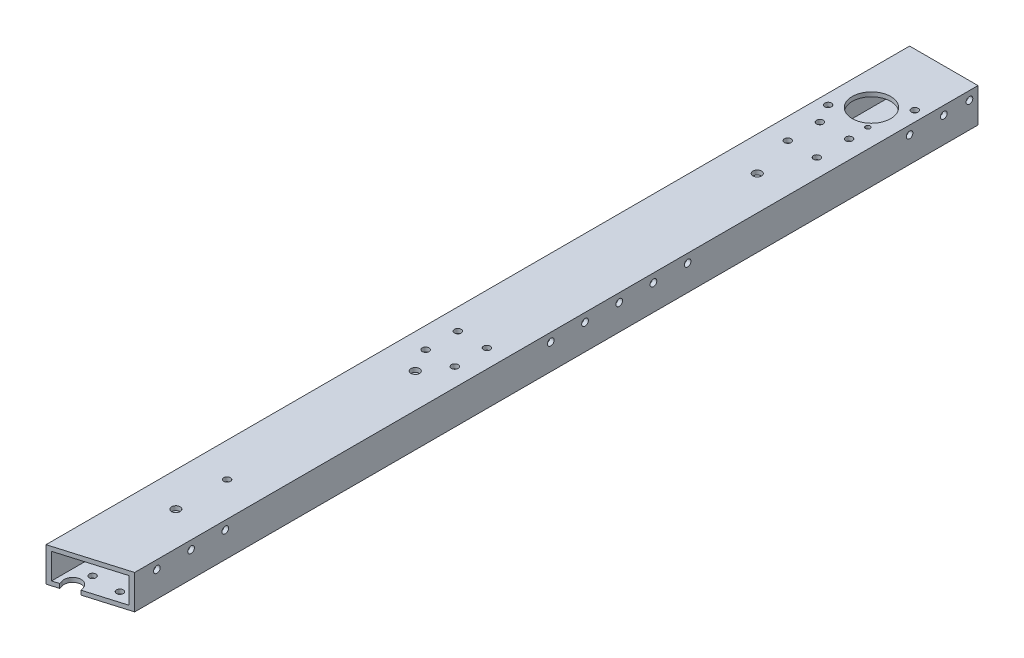
SolidWorks part; units mm, degrees
material "6061 Alloy"
ref_plane "Front Plane" through (0, 0, 0) normal (0, 0, 1) x (1, 0, 0)
ref_plane "Top Plane" through (0, 0, 0) normal (0, 1, 0) x (1, 0, 0)
ref_plane "Right Plane" through (0, 0, 0) normal (1, 0, 0) x (0, 0, -1)
sketch "Sketch1" plane through (0, 0, 0) normal (0, 0, 1) x (1, 0, 0)
  line L0 (-22.225, 9.525) -> (22.225, 9.525)
  line L2 (-25.4, 12.7) -> (25.4, 12.7)
  line L3 (-25.4, 12.7) -> (-25.4, -12.7)
  line L4 (-25.4, -12.7) -> (25.4, -12.7)
  line L5 (25.4, 12.7) -> (25.4, -12.7)
  line L10 (22.225, 9.525) -> (22.225, -9.525)
  line L11 (-22.225, -9.525) -> (22.225, -9.525)
  line L12 (-22.225, 9.525) -> (-22.225, -9.525)
  point P12 (0, 12.7)
  point P14 (25.4, 0)
  dimension "Wall Thickness" = 3.175
  dimension "Outside Width" = 50.8
  dimension "Outside Height" = 25.4
  dimension "Inside Height" = 19.05
  dimension "Inside Width" = 44.45
sketch "Sketch2" plane through (0, 0, 0) normal (1, 0, 0) x (0, 0, -1)
  line L0 (320.675, 0) -> (-320.675, 0)
  point P4 (0, 0)
  point P7 (-320.675, 0)
  point P10 (320.675, 0)
  dimension "Length" = 641.35
sketch "Sketch3" plane through (0, 0, 0) normal (0, 0, 1) x (1, 0, 0)
  line L21 (25.4, 12.7) -> (-25.4, 12.7)
  line L22 (25.4, -12.7) -> (25.4, 12.7)
  line L23 (-25.4, -12.7) -> (25.4, -12.7)
  line L24 (-25.4, 12.7) -> (-25.4, -12.7)
  line L25 (25.4, 12.7) -> (-25.4, 12.7)
  line L26 (25.4, -12.7) -> (25.4, 12.7)
  line L27 (-25.4, -12.7) -> (25.4, -12.7)
  line L28 (-25.4, 12.7) -> (-25.4, -12.7)
  line L29 (22.225, 9.525) -> (-22.225, 9.525)
  line L30 (22.225, -9.525) -> (22.225, 9.525)
  line L31 (-22.225, -9.525) -> (22.225, -9.525)
  line L32 (-22.225, 9.525) -> (-22.225, -9.525)
  line L33 (22.225, 9.525) -> (-22.225, 9.525)
  line L34 (22.225, -9.525) -> (22.225, 9.525)
  line L35 (-22.225, -9.525) -> (22.225, -9.525)
  line L36 (-22.225, 9.525) -> (-22.225, -9.525)
  dimension "D1" = 0
  dimension "D2" = 0
extrude "Boss-Extrude1" add sketch "Sketch3" along normal up to vertex (320.675 mm away) and the other way up to vertex (320.675 mm away) up to point (0, 0, 320.675) other way up to point (0, 0, -320.675)
sketch "Drawing Reference" plane through (0, 0, 0) normal (1, 0, 0) x (0, 0, -1)
  line L0 (-320.675, 0) -> (320.675, 0) construction
  line L1 (0, -12.7) -> (0, 12.7) construction
  line L2 (-320.675, -12.7) -> (320.675, -12.7) construction
  line L5 (-320.675, 12.7) -> (320.675, 12.7) construction
  point P7 (-284.099, 0)
  point P8 (284.099, 0)
  dimension "D1" = 36.576
sketch "Sketch4" plane through (0, 12.7, 0) normal (0, 1, 0) x (1, 0, 0)
  line L0 (-25.4, -320.675) -> (25.4, -305.6274)
  line L1 (25.4, -320.675) -> (25.4, 320.675) construction
  line L2 (25.4, -320.675) -> (-25.4, -320.675)
  dimension "D1" = 16.5
extrude "Cut-Extrude1" cut sketch "Sketch4" against normal through all and the other way through all flip side to cut
sketch "Sketch8" plane through (0, 12.7, 0) normal (0, 1, 0) x (1, 0, 0)
  line L0 (0, 320.675) -> (0, 266.954) construction
  line L1 (25.4, 320.675) -> (-25.4, 320.675) construction
  circle A0 centre (0, 266.954) radius 14.2875
  dimension "D1" = 53.721
extrude "Cut-Extrude2" cut sketch "Sketch8" against normal through all
sketch "Sketch9" plane through (0, -12.7, 0) normal (0, -1, 0) x (1, 0, 0)
  line L0 (-12.7762, 284.753) -> (-10.2362, 301.263) construction
  line L1 (-10.2362, 301.263) -> (10.0838, 301.263) construction
  line L2 (10.0838, 301.263) -> (12.6238, 284.753) construction
  line L3 (12.6238, 284.753) -> (-12.7762, 284.753) construction
  point P3 (0, 0)
  point P4 (10.0838, 301.263)
  point P6 (-10.2362, 301.263)
hole_wizard "#10 Clearance Hole1" positions "Sketch10" profile "Sketch11" hole size "#10" standard "ANSI Inch"
sketch "Sketch10" plane through (0, -12.7, 0) normal (0, -1, 0) x (-1, 0, 0)
  point P0 (-12.6238, -284.753)
  point P3 (12.7762, -284.753)
  point P6 (10.2362, -301.263)
  point P9 (-10.0838, -301.263)
  point P12 (10.2362, -301.263)
  point P14 (-10.0838, -301.263)
sketch "Sketch11" plane through (12.6238, -12.7, 284.753) normal (1, 0, 0) x (0, 0, -1)
  line L0 (0, 0) -> (0, 6.5757)
  line L1 (0, 6.5757) -> (2.4892, 5.08)
  line L2 (2.4892, 5.08) -> (2.4892, 0)
  line L5 (2.4892, 0) -> (0, 0)
  line L10 (0, 6.5757) -> (-2.4892, 5.08) construction
  line L11 (0, -6.35) -> (0, 107.95) construction
  dimension "Hole Dia." = 4.9784
  dimension "Hole Depth" = 5.08
  dimension "Drill Angle" = 118
sketch "Sketch12" plane through (25.4, 0, 0) normal (1, 0, 0) x (0, 0, -1)
  line L0 (320.675, 533.4) -> (-305.6274, 533.4) construction
  line L1 (320.675, 520.7) -> (320.675, 546.1) construction
  line L2 (-305.6274, 546.1) -> (-305.6274, 520.7) construction
hole_wizard "#10 Clearance Hole2" positions "Sketch13" profile "Sketch14" hole size "#10" standard "ANSI Inch" end condition through all
sketch "Sketch13" plane through (25.4, 0, 0) normal (1, 0, 0) x (0, 0, -1)
  point P0 (314.325, 6.35)
  point P3 (295.275, 6.35)
sketch "Sketch14" plane through (25.4, 6.35, -314.325) normal (0, 1, 0) x (0, 0, -1)
  line L0 (0, 0) -> (0, 50.8)
  line L1 (0, 50.8) -> (2.4892, 50.8)
  line L2 (2.4892, 50.8) -> (2.4892, 0)
  line L5 (2.4892, 0) -> (0, 0)
  line L11 (0, -6.35) -> (0, 107.95) construction
  dimension "Thru Hole Dia." = 4.9784
  dimension "Thru Hole Depth" = 50.8
hole_wizard "#10 Clearance Hole3" positions "Sketch15" profile "Sketch16" hole size "#10" standard "ANSI Inch" end condition through all
sketch "Sketch15" plane through (25.4, 0, 0) normal (1, 0, 0) x (0, 0, -1)
  point P0 (105.029, 6.35)
  point P3 (79.629, 6.35)
  point P6 (54.229, 6.35)
  point P9 (28.829, 6.35)
  point P12 (3.429, 6.35)
  point P24 (-289.1267, 6.3882)
  point P27 (-263.7267, 6.3882)
  point P30 (-238.3267, 6.3882)
sketch "Sketch16" plane through (25.4, 6.35, -105.029) normal (0, 1, 0) x (0, 0, -1)
  line L0 (0, 0) -> (0, 50.8)
  line L1 (0, 50.8) -> (2.4892, 50.8)
  line L2 (2.4892, 50.8) -> (2.4892, 0)
  line L5 (2.4892, 0) -> (0, 0)
  line L11 (0, -6.35) -> (0, 107.95) construction
  dimension "Thru Hole Dia." = 4.9784
  dimension "Thru Hole Depth" = 50.8
sketch "Sketch18" plane through (0, 12.7, 0) normal (0, 1, 0) x (1, 0, 0)
  line L0 (-17.786, 252.537) -> (17.786, 281.371) construction
  line L1 (0, 266.954) -> (11.3559, 252.9444) construction
hole_wizard "#10 Clearance Hole4" positions "Sketch19" profile "Sketch20" hole size "#10" standard "ANSI Inch"
sketch "Sketch19" plane through (0, 12.7, 0) normal (0, 1, 0) x (1, 0, 0)
  point P0 (17.786, 281.371)
  point P3 (-17.786, 252.537)
sketch "Sketch20" plane through (17.786, 12.7, -281.371) normal (1, 0, 0) x (0, 0, 1)
  line L0 (0, 0) -> (0, 6.5757)
  line L1 (0, 6.5757) -> (2.4892, 5.08)
  line L2 (2.4892, 5.08) -> (2.4892, 0)
  line L5 (2.4892, 0) -> (0, 0)
  line L10 (0, 6.5757) -> (-2.4892, 5.08) construction
  line L11 (0, -6.35) -> (0, 107.95) construction
  dimension "Hole Dia." = 4.9784
  dimension "Hole Depth" = 5.08
  dimension "Drill Angle" = 118
sketch "Sketch21" plane through (0, 12.7, 0) normal (0, 1, 0) x (1, 0, 0)
  line L2 (-0.0762, -211.5512) -> (0, -313.1512) construction
  line L3 (-25.4, -320.675) -> (25.4, -305.6274) construction
  dimension "D1" = 101.6
hole_wizard "#10 Clearance Hole5" positions "Sketch22" profile "Sketch23" hole size "#10" standard "ANSI Inch" end condition through all
sketch "Sketch22" plane through (0, 12.7, 0) normal (0, 1, 0) x (1, 0, 0)
  point P0 (-0.0762, -211.5512)
sketch "Sketch23" plane through (-0.0762, 12.7, 211.5512) normal (1, 0, 0) x (0, 0, 1)
  line L0 (0, 0) -> (0, 25.4)
  line L1 (0, 25.4) -> (2.4892, 25.4)
  line L2 (2.4892, 25.4) -> (2.4892, 0)
  line L5 (2.4892, 0) -> (0, 0)
  line L11 (0, -6.35) -> (0, 107.95) construction
  dimension "Thru Hole Dia." = 4.9784
  dimension "Thru Hole Depth" = 25.4
hole_wizard "Tap Drill for #8-32 Tap1" positions "Sketch24" profile "Sketch25" hole size "#8-32" standard "ANSI Inch" end condition through all
sketch "Sketch24" plane through (0, 12.7, 0) normal (0, 1, 0) x (1, 0, 0)
  point P0 (11.3559, 252.9444)
sketch "Sketch25" plane through (11.3559, 12.7, -252.9444) normal (1, 0, 0) x (0, 0, 1)
  line L0 (0, 0) -> (0, 25.4)
  line L1 (0, 25.4) -> (1.7272, 25.4)
  line L2 (1.7272, 25.4) -> (1.7272, 0)
  line L5 (1.7272, 0) -> (0, 0)
  line L11 (0, -6.35) -> (0, 107.95) construction
  dimension "Thru Hole Dia." = 3.4544
  dimension "Thru Hole Depth" = 25.4
hole_wizard "#10 Clearance Hole6" positions "Sketch26" profile "Sketch27" hole size "#10" standard "ANSI Inch" end condition through all
sketch "Sketch26" plane through (0, 12.7, 0) normal (0, 1, 0) x (1, 0, 0)
  point P0 (-9.7957, 238.4743)
  point P3 (11.8451, 238.4743)
  point P6 (11.8451, 214.5983)
  point P9 (-9.7957, 214.5983)
  point P12 (11.8451, -30.4483)
  point P15 (-9.7957, -30.4483)
  point P18 (-9.7957, -54.3243)
  point P21 (11.8451, -54.3243)
sketch "Sketch27" plane through (-9.7957, 12.7, -238.4743) normal (1, 0, 0) x (0, 0, 1)
  line L0 (0, 0) -> (0, 25.4)
  line L1 (0, 25.4) -> (5.2197, 25.4)
  line L2 (2.4892, 22.2589) -> (2.4892, 0)
  line L5 (2.4892, 0) -> (0, 0)
  line L7 (5.2197, 25.4) -> (2.4892, 22.2589)
  line L8 (-5.2197, 25.4) -> (-2.4892, 22.2589) construction
  line L11 (0, -6.35) -> (0, 107.95) construction
  dimension "Thru Hole Dia." = 4.9784
  dimension "Thru Hole Depth" = 25.4
  dimension "Far C'Sink Dia." = 10.4394
  dimension "Far C'Sink Angle" = 82
hole_wizard "#10 (0.1935) Diameter Hole1" positions "Sketch28" profile "Sketch29" hole size "#10" standard "ANSI Inch"
sketch "Sketch28" plane through (25.4, 0, 0) normal (1, 0, 0) x (0, 0, -1)
  point P5 (269.875, 6.35)
sketch "Sketch29" plane through (25.4, 6.35, -269.875) normal (0, 1, 0) x (0, 0, -1)
  line L0 (0, 0) -> (0, 4.7786)
  line L1 (0, 4.7786) -> (2.4574, 3.302)
  line L2 (2.4574, 3.302) -> (2.4574, 0)
  line L5 (2.4574, 0) -> (0, 0)
  line L10 (0, 4.7786) -> (-2.4574, 3.302) construction
  line L11 (0, -6.35) -> (0, 107.95) construction
  dimension "Hole Dia." = 4.9149
  dimension "Hole Depth" = 3.302
  dimension "Drill Angle" = 118
sketch "Sketch30" plane through (0, -12.7, 0) normal (0, 1, 0) x (1, 0, 0)
  line L0 (-25.4, -320.675) -> (-11.4451, -316.5414) construction
  line L1 (-25.4, -320.675) -> (25.4, -305.6274) construction
  line L2 (-11.4451, -316.5414) -> (-12.1665, -314.106) construction
  line L3 (-5.3566, -314.7379) -> (-6.078, -312.3025)
  line L4 (-17.5337, -318.3449) -> (-18.2551, -315.9095)
  line L5 (-5.3566, -314.7379) -> (-17.5337, -318.3449)
  arc A0 (-6.078, -312.3025) -> (-18.2551, -315.9095) centre (-12.1665, -314.106) ccw
  line M41 (25.4, -305.6274) -> (-25.4, -320.675)
  dimension "D1" = 6.35
  dimension "D3" = 2.54
  dimension "D2" = 6.35
extrude "Cut-Extrude4" cut sketch "Sketch30" along normal blind 5.08 contours A0 L3 L4 M41 region at (-12.552, -12.7, 312.8048)
sketch "Sketch31" plane through (0, 12.7, 0) normal (0, 1, 0) x (1, 0, 0)
  line L0 (0, -313.1512) -> (0, -249.6512) construction
  line L1 (-25.4, -320.675) -> (25.4, -305.6274) construction
  line L2 (0, -249.6512) -> (0, -71.8512) construction
  line L3 (0, -71.8512) -> (0, 182.1488) construction
  dimension "D1" = 63.5
  dimension "D2" = 177.8
  dimension "D3" = 254
hole_wizard "1/4 (0.25) Diameter Hole1" positions "Sketch32" profile "Sketch33" hole size "1/4" standard "ANSI Inch" end condition through all
sketch "Sketch32" plane through (0, 12.7, 0) normal (0, 1, 0) x (1, 0, 0)
  point P9 (0, -71.8512)
  point P12 (0, -249.6512)
  point P15 (0, 182.1488)
sketch "Sketch33" plane through (0, 12.7, 71.8512) normal (1, 0, 0) x (0, 0, 1)
  line L0 (0, 0) -> (0, 25.4)
  line L1 (0, 25.4) -> (3.175, 25.4)
  line L2 (3.175, 25.4) -> (3.175, 0)
  line L5 (3.175, 0) -> (0, 0)
  line L11 (0, -6.35) -> (0, 107.95) construction
  dimension "Thru Hole Dia." = 6.35
  dimension "Thru Hole Depth" = 25.4
equation "\"D1@Drawing Reference\"=\"Outside Width@Sketch1\" * 0.72"
